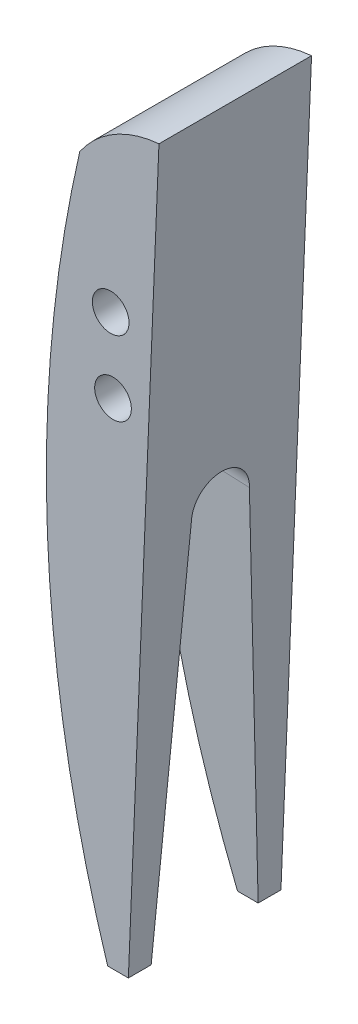
SolidWorks part; units mm, degrees
material "Polyester Resin"
ref_plane "Front Plane" through (0, 0, 0) normal (0, 0, 1) x (1, 0, 0)
ref_plane "Top Plane" through (0, 0, 0) normal (0, 1, 0) x (1, 0, 0)
ref_plane "Right Plane" through (0, 0, 0) normal (1, 0, 0) x (0, 0, -1)
sketch "Sketch1" plane through (0, 0, 0) normal (0, 0, 1) x (1, 0, 0)
  line L0 (23.5472, 52.9813) -> (117.7362, 52.9813) construction
  line L1 (74.1004, 88.8984) -> (71.9414, 36.8284)
  line L2 (672, 1512) -> (3360, 1512) construction
  arc A1 (68.8934, 85.8504) -> (71.9414, 36.8284) centre (153.1846, 66.4856) ccw
  circle A2 centre (70.9254, 77.7224) radius 1.2065
  circle A3 centre (71.0778, 72.8964) radius 1.2065
  arc A5 (74.1004, 88.8984) -> (68.8934, 85.8504) centre (74.7079, 81.8889) ccw
  dimension "D3" = 11.176
  dimension "D4" = 8.128
  dimension "D5" = 2.413
  dimension "D1" = 7.0358
  dimension "D7" = 86.487
  dimension "D2" = 3.175
  dimension "D6" = 2.032
  dimension "D8" = 40.894
  dimension "D9" = 1.016
  dimension "D10" = 4.826
  dimension "D11" = 0.1524
extrude "Boss-Extrude1" add sketch "Sketch1" along normal blind 10.033
sketch "Sketch2" plane through (70.2935, -2.9146, 0) normal (0.9991, -0.0414, 0) x (0, 0, -1)
  line L1 (-10.033, 39.7772) -> (0, 39.7772) construction
  line L3 (-1.27, 39.7772) -> (-8.763, 39.7772)
  line L4 (-10.033, 39.7772) -> (-10.033, 91.8919) construction
  line L5 (0, 39.7772) -> (0, 91.8919) construction
  line L6 (-8.763, 39.7772) -> (-6.9215, 68.3522)
  line L7 (-1.27, 39.7772) -> (-3.1115, 68.3522)
  arc A0 (-3.1115, 68.3522) -> (-6.9215, 68.3522) centre (-5.0165, 68.3522) ccw
  dimension "D4" = 3.81
  dimension "D1" = 1.27
  dimension "D2" = 1.27
  dimension "D3" = 28.575
extrude "Cut-Extrude1" cut sketch "Sketch2" against normal blind 10.033
sketch "Sketch3" plane through (0, 0, 10.033) normal (0, 0, 1) x (1, 0, 0)
  line L0 (70.7284, 40.3898) -> (72.089, 40.3898)
  line L1 (71.9414, 36.8284) -> (74.1004, 88.8984) construction
  line L2 (82.9805, 40.3898) -> (71.4235, 40.3898) construction
  line L3 (72.089, 40.3898) -> (71.9414, 36.8284)
  arc A0 (68.8934, 85.8504) -> (71.9414, 36.8284) centre (153.1846, 66.4856) ccw construction
  arc A1 (70.7284, 40.3898) -> (71.9414, 36.8284) centre (153.1846, 66.4856) ccw
  arc A2 (66.7016, 65.6452) -> (71.9414, 36.8284) centre (153.1846, 66.4856) ccw construction
extrude "Cut-Extrude2" cut sketch "Sketch3" against normal up to surface (10.033 mm away) up to face at (70.3462, 70.6476, 0)
